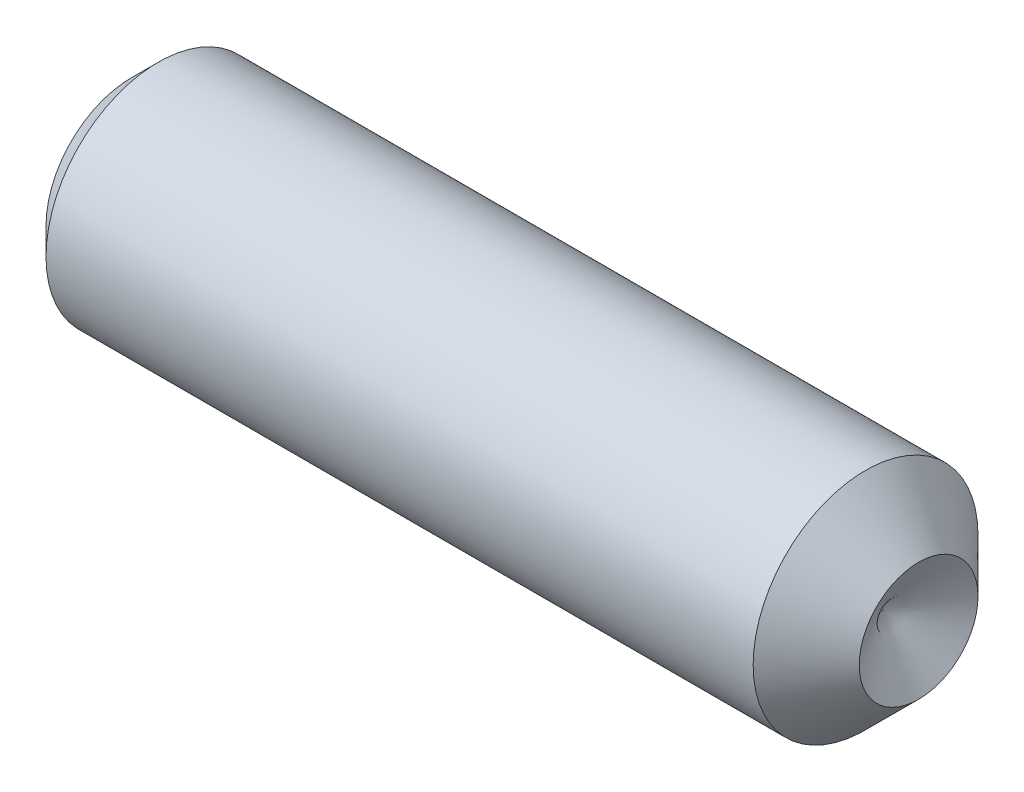
SolidWorks part; units mm, degrees
revolve "BaseBody" add sketch "BodySke" angle 360 about L5 other way angle 60
sketch "BodySke" plane through (0, 0, 0) normal (0, 0, 1) x (1, 0, 0)
  line L0 (0, 0) -> (0, 2.4194)
  line L1 (0, 2.4194) -> (0.7557, 3.175)
  line L2 (0.7557, 3.175) -> (20.7264, 3.175)
  line L3 (20.7264, 3.175) -> (22.225, 1.6764)
  line L4 (21.2177, 0) -> (0, 0)
  line L5 (-12.7, 0) -> (88.9, 0) construction
  line L6 (21.2177, 0) -> (22.225, 1.6764)
  line L7 (22.225, 1.6764) -> (22.225, 11.2014) construction
  line L8 (0, -2.4193) -> (0.7557, -3.175) construction
  line L9 (21.2177, 0) -> (22.225, -1.6764) construction
  line L10 (20.7264, -3.175) -> (22.225, -1.6764) construction
  line L11 (1.27, 15.875) -> (1.27, -3.175) construction
  dimension "Length" = 22.225
  dimension "Diameter" = 6.35
cosmetic thread "ThreadCosmetic" [suppressed] parameters "Thread_minor"=4.8387
ref_plane "Plane1" through (0, 0, 0) normal (0, 0, 1) x (1, 0, 0)
ref_plane "Plane2" through (0, 0, 0) normal (0, 1, 0) x (1, 0, 0)
ref_plane "Plane3" through (0, 0, 0) normal (1, 0, 0) x (0, 0, -1)
sketch "Sketch2" plane through (0, 0, 0) normal (-1, 0, 0) x (0, 0, 1)
  line L0 (0.9165, 1.5875) -> (-0.9165, 1.5875)
  line L1 (-0.9165, 1.5875) -> (-1.8331, 0)
  line L2 (0.9165, 1.5875) -> (1.8331, 0)
  line L3 (0.9165, -1.5875) -> (1.8331, 0)
  line L4 (0.9165, -1.5875) -> (-0.9165, -1.5875)
  line L5 (-0.9165, -1.5875) -> (-1.8331, 0)
  dimension "D2" = 1.5875
  dimension "D3" = 1.5875
extrude "Hex" cut sketch "Sketch2" against normal blind 3.175
sketch "Sketch4" plane through (0, 4.7709, -0.5249) normal (-1, 0, 0) x (0, 0, 1)
  line L0 (0.5249, -4.7709) -> (2.4172, -4.7709)
  line L1 (0.5249, -4.7709) -> (6.6732, -1.2211) construction
  line L2 (0.5249, -4.7709) -> (1.471, -3.1321)
  line L3 (2.0912, -4.3358) -> (2.3286, -4.1988)
  line L4 (1.6848, -3.6319) -> (1.9222, -3.4948)
  arc A0 (2.0912, -4.3358) -> (1.6848, -3.6319) centre (0.5249, -4.7709) ccw
  arc A1 (2.4172, -4.7709) -> (2.3286, -4.1988) centre (0.5249, -4.7709) ccw
  arc A2 (1.471, -3.1321) -> (1.9222, -3.4948) centre (0.5249, -4.7709) cw
  circle A3 centre (0.5249, -4.7709) radius 1.6256 construction
  circle A4 centre (0.5249, -4.7709) radius 1.8923 construction
  dimension "Spline_n_dim" = 3.2512
  dimension "Spline_m_dim" = 3.7846
  dimension "D1" = 30
  dimension "Spline_p_dim" = 0.8128
  dimension "D3" = 0.4064
extrude "Spline" [suppressed] cut sketch "Sketch4" against normal blind 3.175
pattern_circular "CirPattern1" [suppressed] count 6 every 60 about axis through (-12.7, 0, 0) along (1, 0, 0)
sketch "ThdSchSke" plane through (0, 0, 0) normal (0, 0, 1) x (1, 0, 0)
  line L0 (0.7557, -2.4193) -> (0.2265, -3.175)
  line L1 (0.7557, -2.4193) -> (1.2848, -3.175)
  line L2 (1.2848, -3.175) -> (1.2848, -3.9688)
  line L3 (-3.175, 0) -> (5.1513, 0) construction
  line L4 (0.7557, 3.175) -> (0.7557, -3.175) construction
  line L5 (1.2848, -3.9688) -> (0.2265, -3.9688)
  line L6 (0.2265, -3.9688) -> (0.2265, -3.175)
  dimension "Thread_minor" = 4.8387
  dimension "Diameter" = 6.35
revolve "ThreadSchematic" [suppressed] cut sketch "ThdSchSke" angle 360 about L3
pattern_linear "ThdSchPat" [suppressed]
equation "\"D2@Sketch2\" = \"Hex_size@Sketch2\" / 2"
equation "\"D3@Sketch2\" = \"Hex_size@Sketch2\" / 2"
equation "\"Thread_minor@ThreadCosmetic\" = \"Minor_dia@BodySke\""
equation "\"D1@Sketch4\" = \"Spline_a_dim@Sketch4\" / 2"
equation "\"D3@Sketch4\" = \"Spline_p_dim@Sketch4\" / 2"
equation "\"D2@CirPattern1\" = \"Spline_a_dim@Sketch4\""
equation "\"Num_teeth@CirPattern1\" = 360 / \"D2@CirPattern1\""
equation "\"Thread_minor@ThdSchSke\" = \"Thread_minor@ThreadCosmetic\""
equation "\"Diameter@ThdSchSke\" = \"Diameter@BodySke\""
equation "\"Overcut@ThdSchSke\" = \"Diameter@BodySke\" * 1.25"
equation "\"Num_threads@ThdSchPat\" = int( (\"Length@BodySke\" - ( ( ( \"Diameter@BodySke\" - \"Minor_dia@BodySke\" ) * 0.5 ) / tan( \"Drive_ch_ang@BodySke\" ) ) - ( ( ( \"Diameter@BodySke\" - \"Cup_dia@BodySke\" ) * 0.5 ) * tan( \"Cup_nose_ang@BodySke\" ) ) ) / \"Advance@BodySke\" + 0.999 )  + 1"
equation "\"Advance@ThdSchPat\" = (\"Length@BodySke\" - ( ( ( \"Diameter@BodySke\" - \"Minor_dia@BodySke\" ) * 0.5 ) / tan( \"Drive_ch_ang@BodySke\" ) ) - ( ( ( \"Diameter@BodySke\" - \"Cup_dia@BodySke\" ) * 0.5 ) * tan( \"Cup_nose_ang@BodySke\"  ) ) ) /  (\"Num_threads@ThdSchPat\" - 1) 'relax it"
equation "' \"Num_threads@ThdSchPat\" = \"Num_threads@ThdSchPat\" - sgn( \"Num_threads@ThdSchPat\" - 1) '---chamfered tips only---"
